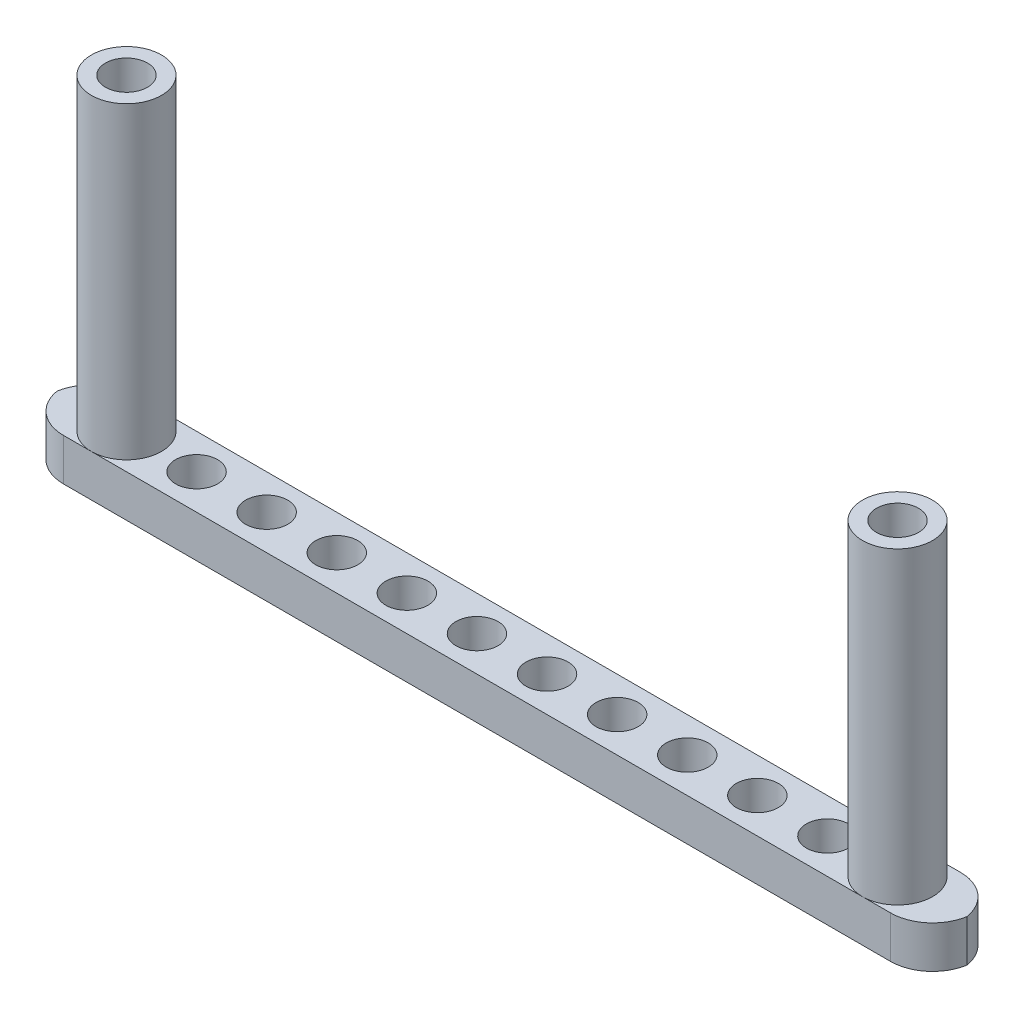
SolidWorks part; units mm, degrees
ref_plane "Front Plane" through (0, 0, 0) normal (0, 0, 1) x (1, 0, 0)
ref_plane "Top Plane" through (0, 0, 0) normal (0, 1, 0) x (1, 0, 0)
ref_plane "Right Plane" through (0, 0, 0) normal (1, 0, 0) x (0, 0, -1)
sketch "Sketch1" plane through (0, 0, 0) normal (0, 1, 0) x (1, 0, 0)
  line L5 (0, 0) -> (65, 0)
  line L6 (0, 0) -> (0, 5)
  line L7 (0, 5) -> (65, 5)
  line L8 (65, 0) -> (65, 5)
  circle A1 centre (5, 2.5) radius 1.5
  circle A2 centre (10, 2.5) radius 1.5
  circle A3 centre (15, 2.5) radius 1.5
  circle A4 centre (20, 2.5) radius 1.5
  circle A5 centre (25, 2.5) radius 1.5
  circle A6 centre (30, 2.5) radius 1.5
  circle A7 centre (35, 2.5) radius 1.5
  circle A8 centre (40, 2.5) radius 1.5
  circle A9 centre (45, 2.5) radius 1.5
  circle A10 centre (50, 2.5) radius 1.5
  circle A11 centre (55, 2.5) radius 1.5
  circle A12 centre (60, 2.5) radius 1.5
  dimension "D1" = 3
  dimension "D3" = 5
  dimension "D2" = 65
  dimension "D4" = 5
  dimension "D5" = 2.5
  dimension "D6" = 12
extrude "Boss-Extrude1" add sketch "Sketch1" along normal blind 3
sketch "Sketch2" plane through (0, 3, 0) normal (0, 1, 0) x (1, 0, 0)
  circle A0 centre (5, 2.5) radius 1.5
  circle A1 centre (5, 2.5) radius 2.5
  circle A2 centre (60, 2.5) radius 1.5
  circle A3 centre (60, 2.5) radius 2.5
  dimension "D1" = 5
  dimension "D2" = 3
  dimension "D3" = 3
extrude "Boss-Extrude2" add sketch "Sketch2" along normal blind 22
fillet "Fillet1" radius 3 4 edges at (65, 1.5, -5) (65, 1.5, 0) (0, 1.5, -5) (0, 1.5, 0)
